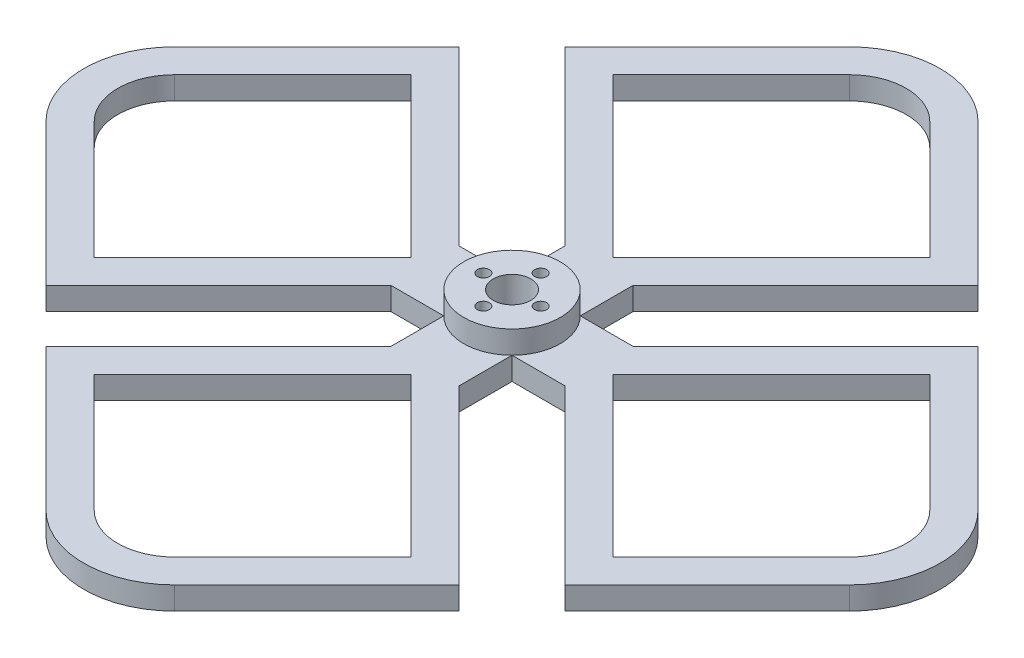
SolidWorks part; units mm, degrees
ref_plane "Front Plane" through (0, 0, 0) normal (0, 0, 1) x (1, 0, 0)
ref_plane "Top Plane" through (0, 0, 0) normal (0, 1, 0) x (1, 0, 0)
ref_plane "Right Plane" through (0, 0, 0) normal (1, 0, 0) x (0, 0, -1)
sketch "Sketch4" plane through (0, 0, 0) normal (0, 1, 0) x (1, 0, 0)
  line L8 (14.7955, 0) -> (72.4487, -57.6532)
  line L9 (14.7955, 0) -> (72.4487, 57.6532)
  line L10 (72.4487, -57.6532) -> (130.102, 0)
  line L11 (72.4487, 57.6532) -> (130.102, 0)
  line L13 (0, 9.525) -> (24.3205, 9.525)
  line L14 (0, 9.525) -> (0, -9.525)
  line L15 (0, -9.525) -> (24.3205, -9.525)
  line L16 (24.3205, 9.525) -> (24.3205, -9.525)
  dimension "D1" = 81.534
  dimension "D2" = 14.7955
  dimension "D3" = 19.05
extrude "Boss-Extrude5" add sketch "Sketch4" along normal blind 6.35 contours L9 L16 L8 L10 L11 | L16 L9 L8 | L14 L15 L8 L9 L13 region at (21.1455, 0, 0) region at (9.9723, 0, 0) region at (73.1586, 0, 0)
sketch "Sketch6" plane through (0, 0, 0) normal (0, 0, 1) x (1, 0, 0)
  line L0 (0, 0) -> (0, 27.64) construction
fillet "Fillet1" radius 25.4 1 edges at (130.102, 3.175, 0)
sketch "Sketch12" plane through (0, 6.35, 0) normal (0, 1, 0) x (1, 0, 0)
  line L14 (72.4487, -44.1829) -> (105.4063, -11.2253)
  line L15 (105.4063, 11.2253) -> (72.4487, 44.1829)
  line L16 (72.4487, 44.1829) -> (28.2659, 0)
  line L20 (28.2659, 0) -> (72.4487, -44.1829)
  line L21 (72.4487, -44.1829) -> (105.4063, -11.2253)
  line L22 (105.4063, 11.2253) -> (72.4487, 44.1829)
  line L23 (72.4487, 44.1829) -> (28.2659, 0)
  line L27 (28.2659, 0) -> (72.4487, -44.1829)
  arc A2 (105.4063, -11.2253) -> (105.4063, 11.2253) centre (94.181, 0) ccw
  arc A3 (105.4063, -11.2253) -> (105.4063, 11.2253) centre (94.181, 0) ccw
  point P0 (0, 0)
  dimension "D1" = 9.525
extrude "Cut-Extrude3" cut sketch "Sketch12" against normal through all
sketch "Sketch11" plane through (0, 0, 0) normal (0, -1, 0) x (1, 0, 0)
  line L7 (72.4487, 57.6532) -> (72.4487, 53.1631)
  line L8 (34.3487, 19.5532) -> (34.3487, 15.0631)
  line L9 (34.3487, -15.0631) -> (34.3487, -19.5532)
  line L10 (72.4487, -53.1631) -> (72.4487, -57.6532)
  line L14 (72.4487, -53.1631) -> (109.8964, -15.7154)
  line L15 (109.8964, 15.7154) -> (72.4487, 53.1631)
  line L16 (72.4487, 53.1631) -> (25.6356, 6.35)
  line L17 (25.6356, 6.35) -> (3.175, 6.35)
  line L18 (3.175, 6.35) -> (3.175, -6.35)
  line L19 (3.175, -6.35) -> (25.6356, -6.35)
  line L20 (25.6356, -6.35) -> (72.4487, -53.1631)
  line L23 (72.4487, 53.1631) -> (34.3487, 15.0631)
  line L27 (34.3487, -15.0631) -> (72.4487, -53.1631)
  line L28 (72.4487, -57.6532) -> (112.1415, -17.9605)
  line L29 (112.1415, 17.9605) -> (72.4487, 57.6532)
  line L30 (72.4487, 57.6532) -> (24.3205, 9.525)
  line L31 (24.3205, 9.525) -> (0, 9.525)
  line L32 (0, 9.525) -> (0, -9.525)
  line L33 (0, -9.525) -> (24.3205, -9.525)
  line L34 (24.3205, -9.525) -> (72.4487, -57.6532)
  line L37 (72.4487, 57.6532) -> (34.3487, 19.5532)
  line L41 (34.3487, -19.5532) -> (72.4487, -57.6532)
  arc A6 (109.8964, -15.7154) -> (109.8964, 15.7154) centre (94.181, 0) ccw
  arc A7 (112.1415, -17.9605) -> (112.1415, 17.9605) centre (94.181, 0) ccw
  dimension "D3" = 38.1
  dimension "D1" = 3.175
  dimension "D2" = 0
pattern_circular "CirPattern7" count 4 over 360 about axis through (0, 0, 0) along (0, 1, 0) of "Boss-Extrude5", "Fillet1", "Cut-Extrude3"
sketch "Sketch13" plane through (0, 6.35, 0) normal (0, 1, 0) x (1, 0, 0)
  circle A0 centre (0, 0) radius 13.4704
extrude "Boss-Extrude8" add sketch "Sketch13" along normal blind 6.35
sketch "Sketch1" plane through (0, 0, 0) normal (0, 1, 0) x (1, 0, 0)
  circle A0 centre (0, 0) radius 2.6905 construction
  circle A1 centre (0, 0) radius 5.227
  circle A2 centre (8, 0) radius 1.6865
  circle A6 centre (0, -8) radius 1.6865
  circle A7 centre (-8, 0) radius 1.6865
  circle A8 centre (0, 8) radius 1.6865
  point P5 (-11.4878, -1.4921)
  point P7 (0, 0)
  point P15 (0, 0)
  dimension "D1" = 10.454
  dimension "D3" = 3.373
  dimension "D2" = 8
extrude "Cut-Extrude1" cut sketch "Sketch1" along normal through all
equation "\"tightTol\"= 0.005in"
equation "\"normTol\"= 0.01in"
equation "\"looseTol\"= 0.02in"
equation "\"D1@Sketch1\"=\"normTol\"+10.2mm"
equation "\"D2@Sketch1\"=8mm"
equation "\"D1@Sketch4\"=3.25-2*\"looseTol\""
equation "\"D2@Sketch4\"=9/16+\"looseTol\""
equation "\"D3@Sketch1\"=3.5mm-\"tightTol\""
